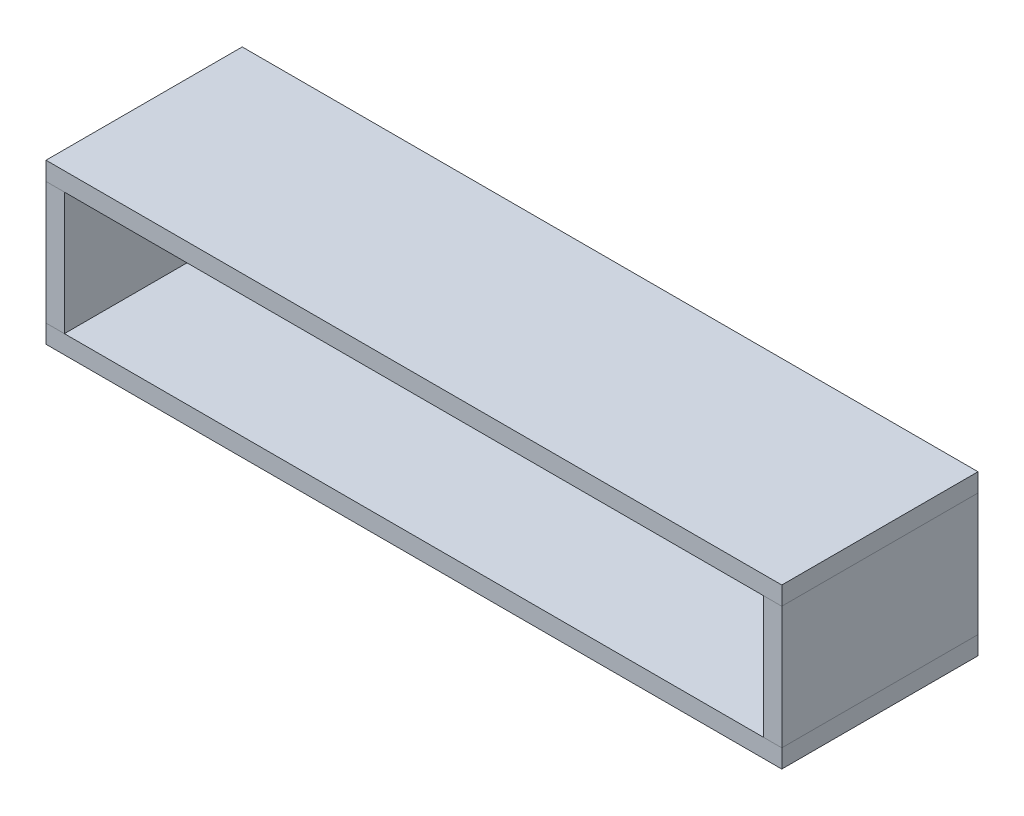
SolidWorks part; units mm, degrees
ref_plane "Front Plane" through (0, 0, 0) normal (0, 0, 1) x (1, 0, 0)
ref_plane "Top Plane" through (0, 0, 0) normal (0, 1, 0) x (1, 0, 0)
ref_plane "Right Plane" through (0, 0, 0) normal (1, 0, 0) x (0, 0, -1)
sketch "Sketch1" plane through (0, 0, 0) normal (0, 1, 0) x (1, 0, 0)
  line L1 (-381, 101.6) -> (381, 101.6)
  line L2 (-381, 101.6) -> (-381, -101.6)
  line L3 (-381, -101.6) -> (381, -101.6)
  line L4 (381, 101.6) -> (381, -101.6)
  line L5 (-381, 101.6) -> (381, -101.6) construction
  line L6 (-381, -101.6) -> (381, 101.6) construction
  point P0 (0, 0)
  dimension "D1" = 762
  dimension "D2" = 203.2
extrude "Boss-Extrude1" add sketch "Sketch1" along normal blind 19.05
sketch "Sketch2" plane through (0, 19.05, 0) normal (0, 1, 0) x (1, 0, 0)
  line L0 (-381, -101.6) -> (381, -101.6) construction
  line L1 (-381, 101.6) -> (-361.95, 101.6)
  line L2 (-381, 101.6) -> (-381, -101.6)
  line L3 (-381, -101.6) -> (-361.95, -101.6)
  line L4 (-361.95, 101.6) -> (-361.95, -101.6)
  line L5 (381, 101.6) -> (-381, 101.6) construction
  line L6 (381, -101.6) -> (361.95, -101.6)
  line L7 (381, -101.6) -> (381, 101.6)
  line L8 (381, 101.6) -> (361.95, 101.6)
  line L9 (361.95, -101.6) -> (361.95, 101.6)
  line L11 (-361.95, 101.6) -> (361.95, 101.6)
  line L12 (-361.95, 101.6) -> (-361.95, 82.55)
  line L13 (-361.95, 82.55) -> (361.95, 82.55)
  line L14 (361.95, 101.6) -> (361.95, 82.55)
  line M7 (381, -101.6) -> (381, 101.6)
  line M8 (381, 101.6) -> (-381, 101.6)
  line M9 (-381, 101.6) -> (-381, -101.6)
  line M10 (-381, -101.6) -> (381, -101.6)
  dimension "D1" = 19.05
  dimension "D2" = 19.05
  dimension "D3" = 19.05
extrude "Boss-Extrude2" add sketch "Sketch2" along normal blind 127 separate body contours L4 M8 M9 M10 | L9 M10 M7 M8 region at (-371.475, 19.05, 0) region at (371.475, 19.05, 0)
extrude "Boss-Extrude3" add sketch "Sketch2<3>" along normal up to surface (127 mm away) separate body contours L4 L13 L9 M8 region at (0, 19.05, -92.075) up to face at (-371.475, 146.05, 0)
sketch "Sketch2<3>" plane through (0, 19.05, 0) normal (0, 1, 0) x (1, 0, 0) same geometry as "Sketch2"
sketch "Sketch3" plane through (0, 146.05, 0) normal (0, 1, 0) x (1, 0, 0)
  line L1 (-381, 101.6) -> (381, 101.6)
  line L2 (-381, 101.6) -> (-381, -101.6)
  line L3 (-381, -101.6) -> (381, -101.6)
  line L4 (381, 101.6) -> (381, -101.6)
extrude "Boss-Extrude4" add sketch "Sketch3" along normal blind 19.05 separate body
